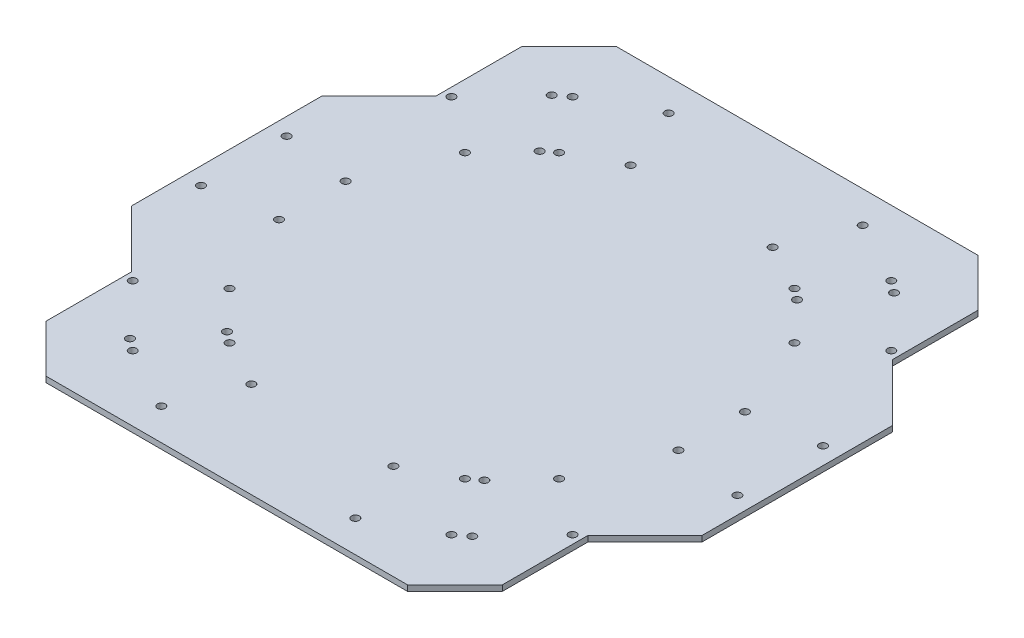
SolidWorks part; units mm, degrees
material "CF-ntbk"
ref_plane "Front Plane" through (0, 0, 0) normal (0, 0, 1) x (1, 0, 0)
ref_plane "Top Plane" through (0, 0, 0) normal (0, 1, 0) x (1, 0, 0)
ref_plane "Right Plane" through (0, 0, 0) normal (1, 0, 0) x (0, 0, -1)
sketch "Sketch1" plane through (0, 0, 0) normal (0, 1, 0) x (1, 0, 0)
  line L0 (-95, 150) -> (-120, 125)
  line L1 (-120, 125) -> (-120, 80)
  line L2 (-120, 80) -> (-150, 50)
  line L3 (-150, 50) -> (-150, -50)
  line L4 (-150, -50) -> (-120, -80)
  line L5 (-120, -80) -> (-120, -125)
  line L6 (-120, -125) -> (-95, -150)
  line L7 (-95, -150) -> (95, -150)
  line L8 (95, -150) -> (120, -125)
  line L9 (120, -125) -> (120, -80)
  line L10 (120, -80) -> (150, -50)
  line L11 (150, -50) -> (150, 50)
  line L12 (150, 50) -> (120, 80)
  line L13 (120, 80) -> (120, 125)
  line L14 (120, 125) -> (95, 150)
  line L15 (95, 150) -> (-95, 150)
  line L17 (-44.2539, 0) -> (44.2539, 0) construction
  line L18 (0, -44.7868) -> (0, 44.7868) construction
  dimension "D2" = 150
  dimension "D1" = 95
  dimension "D3" = 300
  dimension "D4" = 190
  dimension "D5" = 100
  dimension "D6" = 30
  dimension "D7" = 45
  dimension "D8" = 135
extrude "Boss-Extrude1" add sketch "Sketch1" along normal blind 3
sketch "Sketch2" plane through (0, 3, 0) normal (0, 1, 0) x (1, 0, 0)
  line L0 (-79.7985, -138.215) -> (79.7985, 138.215) construction
  line L1 (27.6134, 105.301) -> (76.8653, 76.8653) construction
  line L2 (-69.8318, 120.9522) -> (69.8318, -120.9522) construction
  line L3 (0, -44.7868) -> (0, 44.7868) construction
  line L5 (-44.2539, 0) -> (44.2539, 0) construction
  line L6 (-150.8166, 0) -> (150.8166, 0) construction
  line L7 (-118.217, -118.217) -> (118.217, 118.217) construction
  line L8 (-102.6144, 102.6144) -> (102.6144, -102.6144) construction
  line L9 (105, 17.5) -> (105, -25.4677) construction
  line L11 (30.9172, -103.3935) -> (75.1288, -77.8679) construction
  circle A0 centre (51.0144, 133.3596) radius 2.05
  circle A1 centre (37.3446, 99.6827) radius 2.05
  circle A2 centre (37.3446, -99.6827) radius 2.05
  circle A3 centre (51.0144, -133.3596) radius 2.05
  circle A4 centre (105, 17.5) radius 2.05
  circle A5 centre (141, 22.5) radius 2.05
  circle A12 centre (105, -17.5) radius 2.05
  circle A13 centre (141, -22.5) radius 2.05
  circle A16 centre (89.9856, -110.8596) radius 2.05
  circle A17 centre (67.6554, -82.1827) radius 2.05
  circle A18 centre (89.9856, 110.8596) radius 2.05
  circle A19 centre (67.6554, 82.1827) radius 2.05
  dimension "D1" = 4.1
  dimension "D3" = 30
  dimension "D5" = 30
  dimension "D10" = 45
  dimension "D11" = 45
  dimension "D4" = 17.5
  dimension "D7" = 105
  dimension "D15" = 105
  dimension "D17" = 105
  dimension "D20" = 17.5
  dimension "D24" = 17.5
  dimension "D29" = 17.5
  dimension "D12" = 17.5
  dimension "D16" = 17.5
  dimension "D9" = 22.5
  dimension "D22" = 22.5
  dimension "D23" = 36
  dimension "D26" = 36
  dimension "D8" = 22.5
  dimension "D13" = 22.5
  dimension "D14" = 36
  dimension "D21" = 36
  dimension "D6" = 22.5
  dimension "D18" = 22.5
  dimension "D19" = 36
  dimension "D25" = 36
extrude "HexCut1" cut sketch "Sketch2" against normal up to surface (3 mm away) up to face at (0, 0, 0)
mirror "HexCut2" about plane through (0, 0, 0) normal (1, 0, 0) of "HexCut1"
sketch "ConstructLines" plane through (0, 3, 0) normal (0, 1, 0) x (1, 0, 0)
  line L0 (0, 121.6855) -> (0, -121.6855) construction
  line L1 (-91.1915, 0) -> (91.1915, 0) construction
  line L2 (-44.2539, 0) -> (44.2539, 0) construction
ref_point "Point1"
sketch "Sketch5" plane through (0, 3, 0) normal (0, 1, 0) x (1, 0, 0)
  line L0 (0, 121.6855) -> (0, -121.6855) construction
  line L1 (-91.1915, 0) -> (91.1915, 0) construction
  circle A0 centre (50, 60) radius 1.55
  circle A1 centre (70, 60) radius 1.55
  dimension "D1" = 3.1
  dimension "D2" = 20
  dimension "D3" = 50
  dimension "D4" = 60
  dimension "D5" = 60
extrude "Cut-Extrude2" [suppressed] cut sketch "Sketch5" against normal up to surface (3 mm away) up to face at (-51.0144, 0, -131.3096)
pattern_linear "LPattern1" [suppressed] count 2 spacing 120 along (0, 0, 1) count 2 spacing 120 along (-1, 0, 0) of bodies 111
sketch "Sketch6" plane through (0, 3, 0) normal (0, 1, 0) x (1, 0, 0)
  line L0 (-103.0997, -103.0997) -> (103.0997, 103.0997) construction
  line L1 (0, 121.6855) -> (0, -121.6855) construction
  line L2 (69.8057, 78.6867) -> (81.2763, 67.2162) construction
  line L3 (-98.3117, 98.3117) -> (98.3117, -98.3117) construction
  line L4 (83.4139, -65.0786) -> (62.2362, -86.2562) construction
  circle A0 centre (86.6206, 61.8718) radius 2.05
  circle A1 centre (115.612, 83.7922) radius 2.05
  circle A2 centre (83.7922, 115.612) radius 2.05
  circle A3 centre (61.8718, 86.6206) radius 2.05
  circle A4 centre (86.6206, -61.8718) radius 2.05
  circle A5 centre (61.8718, -86.6206) radius 2.05
  circle A6 centre (83.7922, -115.612) radius 2.05
  circle A7 centre (115.612, -83.7922) radius 2.05
  dimension "D13" = 22.5
  dimension "D14" = 36
  dimension "D6" = 22.5
  dimension "D4" = 4.1
  dimension "D1" = 45
  dimension "D2" = 105
  dimension "D5" = 17.5
  dimension "D7" = 17.5
  dimension "D10" = 105
  dimension "D11" = 17.5
  dimension "D15" = 17.5
  dimension "D17" = 45
  dimension "D3" = 22.5
  dimension "D8" = 36
  dimension "D9" = 36
  dimension "D12" = 22.5
  dimension "D16" = 36
extrude "QuadCut1" cut sketch "Sketch6" against normal up to surface (3 mm away) up to face at (-51.0144, 0, -131.3096)
mirror "QuadCut2" about plane through (0, 0, 0) normal (1, 0, 0) of "QuadCut1"
equation "\"ClampHoleDist\"= 36"
equation "\"ClampDistMid\"=105"
equation "\"Length\"= 300"
equation "\"D3@Sketch1\"=\"Length\""
equation "\"Width\"= 190"
equation "\"D1@Sketch1\"=\"Width\"/2"
equation "\"D2@Sketch1\"=\"Length\"/2"
equation "\"D4@Sketch1\"=\"Width\""
equation "\"D7@Sketch1\"=(\"Length\"- 210)/2"
equation "\"HoleZDist\"=60.000000"
equation "\"D5@Sketch5\"=\"HoleZDist\""
equation "\"D4@Sketch5\"=\"HoleZDist\""
equation "\"HoleXDist\"=50.000000"
equation "\"D3@Sketch5\"=\"HoleXDist\""
equation "\"HoleSpacing\"=20"
equation "\"D2@Sketch5\"=\"HoleSpacing\""
equation "\"D3@LPattern1\"=\"HoleZDist\"*2"
equation "\"D4@LPattern1\"=\"HoleXDist\"*2+(\"HoleSpacing\")"
equation "\"ClampHoriDist\"=17.5"
equation "\"D4@Sketch2\"=\"ClampHoriDist\""
equation "\"D7@Sketch2\"=\"ClampDistMid\""
equation "\"D15@Sketch2\"=\"ClampDistMid\""
equation "\"D17@Sketch2\"=\"ClampDistMid\""
equation "\"D20@Sketch2\"=\"ClampHoriDist\""
equation "\"D24@Sketch2\"=\"ClampHoriDist\""
equation "\"D29@Sketch2\"=\"ClampHoriDist\""
equation "\"D12@Sketch2\"=\"ClampHoriDist\""
equation "\"ClampHoleSize\"=4.1"
equation "\"D1@Sketch2\"=\"ClampHoleSize\""
equation "\"D16@Sketch2\"=\"ClampHoriDist\""
equation "\"D2@Sketch6\"=\"ClampDistMid\""
equation "\"D4@Sketch6\"=\"ClampHoleSize\""
equation "\"D5@Sketch6\"=\"ClampHoriDist\""
equation "\"D7@Sketch6\"=\"ClampHoriDist\""
equation "\"D10@Sketch6\"=\"ClampDistMid\""
equation "\"D11@Sketch6\"=\"ClampHoriDist\""
equation "\"D15@Sketch6\"=\"ClampHoriDist\""
equation "\"FrontClampHoriDist\"=22.5"
equation "\"D9@Sketch2\"=\"FrontClampHoriDist\""
equation "\"D22@Sketch2\"=\"FrontClampHoriDist\""
equation "\"D23@Sketch2\"=\"ClampHoleDist\""
equation "\"D26@Sketch2\"=\"ClampHoleDist\""
equation "\"D8@Sketch2\"=\"FrontClampHoriDist\""
equation "\"D13@Sketch2\"=\"FrontClampHoriDist\""
equation "\"D14@Sketch2\"=\"ClampHoleDist\""
equation "\"D21@Sketch2\"=\"ClampHoleDist\""
equation "\"D6@Sketch2\"=\"FrontClampHoriDist\""
equation "\"D18@Sketch2\"=\"FrontClampHoriDist\""
equation "\"D19@Sketch2\"=\"ClampHoleDist\""
equation "\"D25@Sketch2\"=\"ClampHoleDist\""
equation "\"D3@Sketch6\"=\"FrontClampHoriDist\""
equation "\"D6@Sketch6\"=\"FrontClampHoriDist\""
equation "\"D8@Sketch6\"=\"ClampHoleDist\""
equation "\"D9@Sketch6\"=\"ClampHoleDist\""
equation "\"D12@Sketch6\"=\"FrontClampHoriDist\""
equation "\"D13@Sketch6\"=\"FrontClampHoriDist\""
equation "\"D14@Sketch6\"=\"ClampHoleDist\""
equation "\"D16@Sketch6\"=\"ClampHoleDist\""
